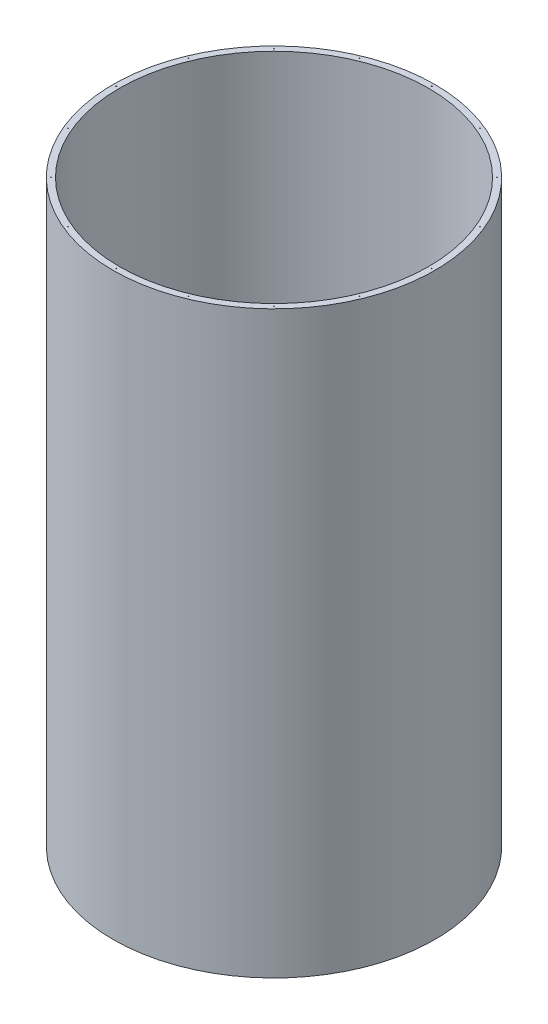
SolidWorks part; units mm, degrees
material "7075-T6 (SN)"
ref_plane "Front Plane" through (0, 0, 0) normal (0, 0, 1) x (1, 0, 0)
ref_plane "Top Plane" through (0, 0, 0) normal (0, 1, 0) x (1, 0, 0)
ref_plane "Right Plane" through (0, 0, 0) normal (1, 0, 0) x (0, 0, -1)
sketch "Sketch1" plane through (0, 0, 0) normal (0, 1, 0) x (1, 0, 0)
  circle A0 centre (0, 0) radius 1250
  circle A1 centre (0, 0) radius 1200
  circle A2 centre (0, 0) radius 1225 construction
  dimension "D1" = 2500
  dimension "D2" = 2450
  dimension "D3" = 2400
extrude "Boss-Extrude1" add sketch "Sketch1" along normal blind 4500
sketch "Sketch2" plane through (0, 4500, 0) normal (0, 1, 0) x (1, 0, 0)
  circle A0 centre (-1225, 0) radius 3.175
  circle A1 centre (0, 0) radius 1225 construction
  circle A2 centre (-1131.7524, 468.7872) radius 3.175
  circle A3 centre (-866.2058, 866.2058) radius 3.175
  circle A4 centre (-468.7872, 1131.7524) radius 3.175
  circle A5 centre (0, 1225) radius 3.175
  circle A6 centre (468.7872, 1131.7524) radius 3.175
  circle A7 centre (866.2058, 866.2058) radius 3.175
  circle A8 centre (1131.7524, 468.7872) radius 3.175
  circle A9 centre (1225, 0) radius 3.175
  circle A10 centre (1131.7524, -468.7872) radius 3.175
  circle A11 centre (866.2058, -866.2058) radius 3.175
  circle A12 centre (468.7872, -1131.7524) radius 3.175
  circle A13 centre (0, -1225) radius 3.175
  circle A14 centre (-468.7872, -1131.7524) radius 3.175
  circle A15 centre (-866.2058, -866.2058) radius 3.175
  circle A16 centre (-1131.7524, -468.7872) radius 3.175
  point P39 (0, 0)
  dimension "D1" = 6.35
  dimension "D3" = 2450
  dimension "D2" = 1225
  dimension "D4" = 16
ref_axis "Axis1" through (0, 4725, 0) along (0, -1, 0)
extrude "Cut-Extrude1" cut sketch "Sketch2" against normal blind 12.7
